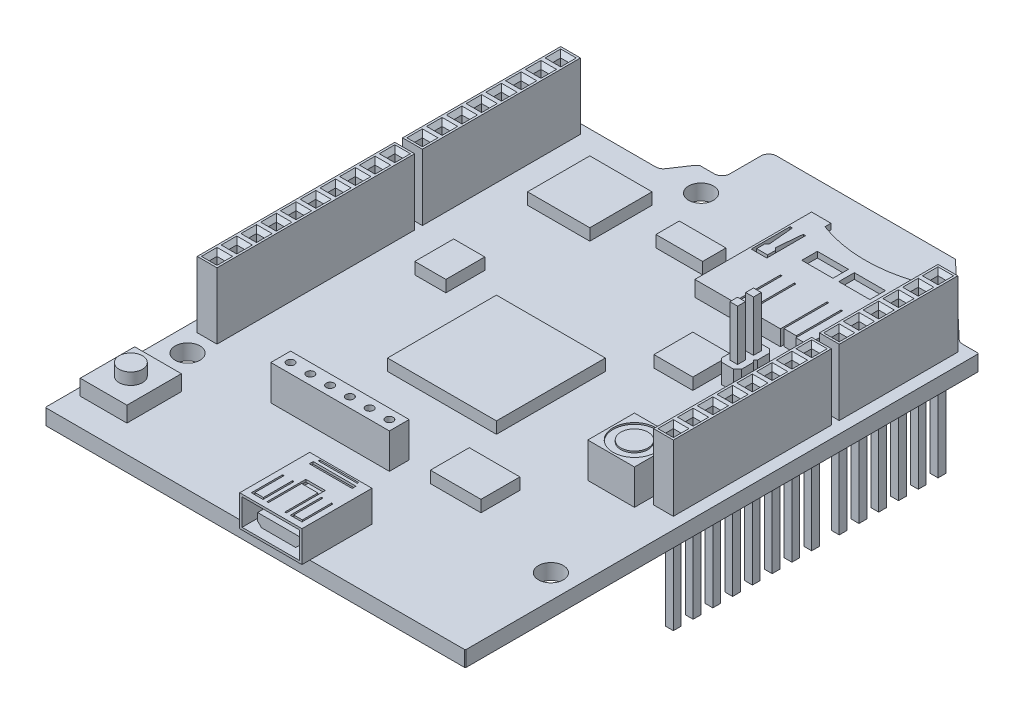
SolidWorks part; units mm, degrees
note: The reader was unsure of these and kept them because the rebuilt part matched: shared geometry of "Esquisse20<2>".
ref_plane "Plan de face" through (0, 0, 0) normal (0, 0, 1) x (1, 0, 0)
ref_plane "Plan de dessus" through (0, 0, 0) normal (0, 1, 0) x (1, 0, 0)
ref_plane "Plan de droite" through (0, 0, 0) normal (1, 0, 0) x (0, 0, -1)
ref_plane "Droite" through (54, 0, 0) normal (1, 0, 0) x (0, 0, -1)
ref_plane "Plaque" through (0, 0, -66) normal (0, 0, 1) x (1, 0, 0)
ref_plane "Arriere" through (0, 0, -75) normal (0, 0, 1) x (1, 0, 0)
ref_plane "Platine" through (0, 2, 0) normal (0, 1, 0) x (1, 0, 0)
ref_plane "Borne" through (0, -11.5, 0) normal (0, 1, 0) x (1, 0, 0)
sketch "Esquisse1" plane through (0, 0, 0) normal (0, 1, 0) x (1, 0, 0)
  line L0 (-55, 66) -> (55, 66) construction
  line L1 (0, 0) -> (54, 0)
  line L2 (0, 0) -> (0, 66)
  line L3 (0, 66) -> (13, 66)
  line L4 (54, 0) -> (54, 66)
  line L5 (54, -55) -> (54, 55) construction
  line L6 (51.5, 66) -> (42, 75)
  line L7 (-55, 75) -> (55, 75) construction
  line L8 (42, 75) -> (18, 75)
  line L9 (18, 75) -> (18, 69)
  line L10 (18, 69) -> (15, 69)
  line L11 (15, 69) -> (13, 66)
  line L12 (51.5, 66) -> (54, 66)
  dimension "D1" = 2.5
  dimension "D2" = 24
  dimension "D3" = 13
  dimension "D4" = 3
  dimension "D5" = 5
  dimension "D6" = 3
extrude "Boss.-Extru.1" add sketch "Esquisse1" along normal up to surface (2 mm away) up to plane "Platine"
sketch "Esquisse2" plane through (0, 2, 0) normal (0, 1, 0) x (1, 0, 0)
  line L0 (2.23, 60.49) -> (3.23, 60.49)
  line L1 (1.46, 64.8) -> (4, 64.8)
  line L2 (1.46, 64.8) -> (1.46, 44.48)
  line L3 (1.46, 44.48) -> (4, 44.48)
  line L4 (4, 64.8) -> (4, 44.48)
  line L5 (1.46, 43.48) -> (4, 43.48)
  line L6 (1.46, 43.48) -> (1.46, 18.08)
  line L7 (1.46, 18.08) -> (4, 18.08)
  line L8 (4, 43.48) -> (4, 18.08)
  line L9 (49.96, 64.8) -> (52.5, 64.8)
  line L10 (49.96, 64.8) -> (49.96, 49.56)
  line L11 (49.96, 49.56) -> (52.5, 49.56)
  line L12 (52.5, 64.8) -> (52.5, 49.56)
  line L13 (49.96, 48.56) -> (52.5, 48.56)
  line L14 (49.96, 48.56) -> (49.96, 28.24)
  line L15 (49.96, 28.24) -> (52.5, 28.24)
  line L16 (52.5, 48.56) -> (52.5, 28.24)
  line L17 (2.23, 63.03) -> (3.23, 63.03)
  line L18 (-1.1, 66) -> (1.1, 66) construction
  line L19 (54, -1.1) -> (54, 1.1) construction
  line L20 (2.73, 18.08) -> (2.73, 43.48) construction
  line L21 (2.73, 44.48) -> (2.73, 64.8) construction
  line L22 (51.23, 28.24) -> (51.23, 48.56) construction
  line L23 (51.23, 49.56) -> (51.23, 64.8) construction
  line L24 (2.23, 21.39) -> (3.23, 21.39)
  line L25 (2.23, 18.85) -> (3.23, 18.85)
  line L26 (2.23, 18.85) -> (2.23, 19.85)
  line L27 (2.23, 19.85) -> (3.23, 19.85)
  line L28 (3.23, 18.85) -> (3.23, 19.85)
  line L29 (2.23, 18.85) -> (3.23, 19.85) construction
  line L30 (2.23, 19.85) -> (3.23, 18.85) construction
  line L31 (2.23, 21.39) -> (2.23, 22.39)
  line L32 (2.23, 22.39) -> (3.23, 22.39)
  line L33 (3.23, 21.39) -> (3.23, 22.39)
  line L34 (2.23, 21.39) -> (3.23, 22.39) construction
  line L35 (2.23, 22.39) -> (3.23, 21.39) construction
  line L36 (2.23, 23.93) -> (3.23, 23.93)
  line L37 (2.23, 23.93) -> (2.23, 24.93)
  line L38 (2.23, 24.93) -> (3.23, 24.93)
  line L39 (3.23, 23.93) -> (3.23, 24.93)
  line L40 (2.23, 23.93) -> (3.23, 24.93) construction
  line L41 (2.23, 24.93) -> (3.23, 23.93) construction
  line L42 (2.23, 26.47) -> (3.23, 26.47)
  line L43 (2.23, 26.47) -> (2.23, 27.47)
  line L44 (2.23, 27.47) -> (3.23, 27.47)
  line L45 (3.23, 26.47) -> (3.23, 27.47)
  line L46 (2.23, 26.47) -> (3.23, 27.47) construction
  line L47 (2.23, 27.47) -> (3.23, 26.47) construction
  line L48 (2.23, 29.01) -> (3.23, 29.01)
  line L49 (2.23, 29.01) -> (2.23, 30.01)
  line L50 (2.23, 30.01) -> (3.23, 30.01)
  line L51 (3.23, 29.01) -> (3.23, 30.01)
  line L52 (2.23, 29.01) -> (3.23, 30.01) construction
  line L53 (2.23, 30.01) -> (3.23, 29.01) construction
  line L54 (2.23, 31.55) -> (3.23, 31.55)
  line L55 (2.23, 31.55) -> (2.23, 32.55)
  line L56 (2.23, 32.55) -> (3.23, 32.55)
  line L57 (3.23, 31.55) -> (3.23, 32.55)
  line L58 (2.23, 31.55) -> (3.23, 32.55) construction
  line L59 (2.23, 32.55) -> (3.23, 31.55) construction
  line L60 (2.23, 34.09) -> (3.23, 34.09)
  line L61 (2.23, 34.09) -> (2.23, 35.09)
  line L62 (2.23, 35.09) -> (3.23, 35.09)
  line L63 (3.23, 34.09) -> (3.23, 35.09)
  line L64 (2.23, 34.09) -> (3.23, 35.09) construction
  line L65 (2.23, 35.09) -> (3.23, 34.09) construction
  line L66 (2.23, 36.63) -> (3.23, 36.63)
  line L67 (2.23, 36.63) -> (2.23, 37.63)
  line L68 (2.23, 37.63) -> (3.23, 37.63)
  line L69 (3.23, 36.63) -> (3.23, 37.63)
  line L70 (2.23, 36.63) -> (3.23, 37.63) construction
  line L71 (2.23, 37.63) -> (3.23, 36.63) construction
  line L72 (2.23, 39.17) -> (3.23, 39.17)
  line L73 (2.23, 39.17) -> (2.23, 40.17)
  line L74 (2.23, 40.17) -> (3.23, 40.17)
  line L75 (3.23, 39.17) -> (3.23, 40.17)
  line L76 (2.23, 39.17) -> (3.23, 40.17) construction
  line L77 (2.23, 40.17) -> (3.23, 39.17) construction
  line L78 (2.23, 41.71) -> (3.23, 41.71)
  line L79 (2.23, 41.71) -> (2.23, 42.71)
  line L80 (2.23, 42.71) -> (3.23, 42.71)
  line L81 (3.23, 41.71) -> (3.23, 42.71)
  line L82 (2.23, 41.71) -> (3.23, 42.71) construction
  line L83 (2.23, 42.71) -> (3.23, 41.71) construction
  line L84 (2.23, 63.03) -> (2.23, 64.03)
  line L85 (2.23, 64.03) -> (3.23, 64.03)
  line L86 (3.23, 63.03) -> (3.23, 64.03)
  line L87 (2.23, 63.03) -> (3.23, 64.03) construction
  line L88 (2.23, 64.03) -> (3.23, 63.03) construction
  line L89 (2.23, 60.49) -> (2.23, 61.49)
  line L90 (2.23, 61.49) -> (3.23, 61.49)
  line L91 (3.23, 60.49) -> (3.23, 61.49)
  line L92 (2.23, 60.49) -> (3.23, 61.49) construction
  line L93 (2.23, 61.49) -> (3.23, 60.49) construction
  line L94 (2.23, 57.95) -> (3.23, 57.95)
  line L95 (2.23, 57.95) -> (2.23, 58.95)
  line L96 (2.23, 58.95) -> (3.23, 58.95)
  line L97 (3.23, 57.95) -> (3.23, 58.95)
  line L98 (2.23, 57.95) -> (3.23, 58.95) construction
  line L99 (2.23, 58.95) -> (3.23, 57.95) construction
  line L100 (2.23, 55.41) -> (3.23, 55.41)
  line L101 (2.23, 55.41) -> (2.23, 56.41)
  line L102 (2.23, 56.41) -> (3.23, 56.41)
  line L103 (3.23, 55.41) -> (3.23, 56.41)
  line L104 (2.23, 55.41) -> (3.23, 56.41) construction
  line L105 (2.23, 56.41) -> (3.23, 55.41) construction
  line L106 (2.23, 52.87) -> (3.23, 52.87)
  line L107 (2.23, 52.87) -> (2.23, 53.87)
  line L108 (2.23, 53.87) -> (3.23, 53.87)
  line L109 (3.23, 52.87) -> (3.23, 53.87)
  line L110 (2.23, 52.87) -> (3.23, 53.87) construction
  line L111 (2.23, 53.87) -> (3.23, 52.87) construction
  line L112 (2.23, 50.33) -> (3.23, 50.33)
  line L113 (2.23, 50.33) -> (2.23, 51.33)
  line L114 (2.23, 51.33) -> (3.23, 51.33)
  line L115 (3.23, 50.33) -> (3.23, 51.33)
  line L116 (2.23, 50.33) -> (3.23, 51.33) construction
  line L117 (2.23, 51.33) -> (3.23, 50.33) construction
  line L118 (2.23, 47.79) -> (3.23, 47.79)
  line L119 (2.23, 47.79) -> (2.23, 48.79)
  line L120 (2.23, 48.79) -> (3.23, 48.79)
  line L121 (3.23, 47.79) -> (3.23, 48.79)
  line L122 (2.23, 47.79) -> (3.23, 48.79) construction
  line L123 (2.23, 48.79) -> (3.23, 47.79) construction
  line L124 (2.23, 45.25) -> (3.23, 45.25)
  line L125 (2.23, 45.25) -> (2.23, 46.25)
  line L126 (2.23, 46.25) -> (3.23, 46.25)
  line L127 (3.23, 45.25) -> (3.23, 46.25)
  line L128 (2.23, 45.25) -> (3.23, 46.25) construction
  line L129 (2.23, 46.25) -> (3.23, 45.25) construction
  line L130 (50.73, 60.49) -> (51.73, 60.49)
  line L131 (50.73, 63.03) -> (51.73, 63.03)
  line L132 (50.73, 63.03) -> (50.73, 64.03)
  line L133 (50.73, 64.03) -> (51.73, 64.03)
  line L134 (51.73, 63.03) -> (51.73, 64.03)
  line L135 (50.73, 63.03) -> (51.73, 64.03) construction
  line L136 (50.73, 64.03) -> (51.73, 63.03) construction
  line L137 (50.73, 46.79) -> (51.73, 46.79)
  line L138 (50.73, 46.79) -> (50.73, 47.79)
  line L139 (50.73, 47.79) -> (51.73, 47.79)
  line L140 (51.73, 46.79) -> (51.73, 47.79)
  line L141 (50.73, 46.79) -> (51.73, 47.79) construction
  line L142 (50.73, 47.79) -> (51.73, 46.79) construction
  line L143 (50.73, 60.49) -> (50.73, 61.49)
  line L144 (50.73, 61.49) -> (51.73, 61.49)
  line L145 (51.73, 60.49) -> (51.73, 61.49)
  line L146 (50.73, 60.49) -> (51.73, 61.49) construction
  line L147 (50.73, 61.49) -> (51.73, 60.49) construction
  line L148 (50.73, 57.95) -> (51.73, 57.95)
  line L149 (50.73, 57.95) -> (50.73, 58.95)
  line L150 (50.73, 58.95) -> (51.73, 58.95)
  line L151 (51.73, 57.95) -> (51.73, 58.95)
  line L152 (50.73, 57.95) -> (51.73, 58.95) construction
  line L153 (50.73, 58.95) -> (51.73, 57.95) construction
  line L154 (50.73, 55.41) -> (51.73, 55.41)
  line L155 (50.73, 55.41) -> (50.73, 56.41)
  line L156 (50.73, 56.41) -> (51.73, 56.41)
  line L157 (51.73, 55.41) -> (51.73, 56.41)
  line L158 (50.73, 55.41) -> (51.73, 56.41) construction
  line L159 (50.73, 56.41) -> (51.73, 55.41) construction
  line L160 (50.73, 52.87) -> (51.73, 52.87)
  line L161 (50.73, 52.87) -> (50.73, 53.87)
  line L162 (50.73, 53.87) -> (51.73, 53.87)
  line L163 (51.73, 52.87) -> (51.73, 53.87)
  line L164 (50.73, 52.87) -> (51.73, 53.87) construction
  line L165 (50.73, 53.87) -> (51.73, 52.87) construction
  line L166 (50.73, 50.33) -> (51.73, 50.33)
  line L167 (50.73, 50.33) -> (50.73, 51.33)
  line L168 (50.73, 51.33) -> (51.73, 51.33)
  line L169 (51.73, 50.33) -> (51.73, 51.33)
  line L170 (50.73, 50.33) -> (51.73, 51.33) construction
  line L171 (50.73, 51.33) -> (51.73, 50.33) construction
  line L172 (50.73, 44.25) -> (51.73, 44.25)
  line L173 (50.73, 44.25) -> (50.73, 45.25)
  line L174 (50.73, 45.25) -> (51.73, 45.25)
  line L175 (51.73, 44.25) -> (51.73, 45.25)
  line L176 (50.73, 44.25) -> (51.73, 45.25) construction
  line L177 (50.73, 45.25) -> (51.73, 44.25) construction
  line L178 (50.73, 41.71) -> (51.73, 41.71)
  line L179 (50.73, 41.71) -> (50.73, 42.71)
  line L180 (50.73, 42.71) -> (51.73, 42.71)
  line L181 (51.73, 41.71) -> (51.73, 42.71)
  line L182 (50.73, 41.71) -> (51.73, 42.71) construction
  line L183 (50.73, 42.71) -> (51.73, 41.71) construction
  line L184 (50.73, 39.17) -> (51.73, 39.17)
  line L185 (50.73, 39.17) -> (50.73, 40.17)
  line L186 (50.73, 40.17) -> (51.73, 40.17)
  line L187 (51.73, 39.17) -> (51.73, 40.17)
  line L188 (50.73, 39.17) -> (51.73, 40.17) construction
  line L189 (50.73, 40.17) -> (51.73, 39.17) construction
  line L190 (50.73, 36.63) -> (51.73, 36.63)
  line L191 (50.73, 36.63) -> (50.73, 37.63)
  line L192 (50.73, 37.63) -> (51.73, 37.63)
  line L193 (51.73, 36.63) -> (51.73, 37.63)
  line L194 (50.73, 36.63) -> (51.73, 37.63) construction
  line L195 (50.73, 37.63) -> (51.73, 36.63) construction
  line L196 (50.73, 34.09) -> (51.73, 34.09)
  line L197 (50.73, 34.09) -> (50.73, 35.09)
  line L198 (50.73, 35.09) -> (51.73, 35.09)
  line L199 (51.73, 34.09) -> (51.73, 35.09)
  line L200 (50.73, 34.09) -> (51.73, 35.09) construction
  line L201 (50.73, 35.09) -> (51.73, 34.09) construction
  line L202 (50.73, 31.55) -> (51.73, 31.55)
  line L203 (50.73, 31.55) -> (50.73, 32.55)
  line L204 (50.73, 32.55) -> (51.73, 32.55)
  line L205 (51.73, 31.55) -> (51.73, 32.55)
  line L206 (50.73, 31.55) -> (51.73, 32.55) construction
  line L207 (50.73, 32.55) -> (51.73, 31.55) construction
  line L208 (50.73, 29.01) -> (51.73, 29.01)
  line L209 (50.73, 29.01) -> (50.73, 30.01)
  line L210 (50.73, 30.01) -> (51.73, 30.01)
  line L211 (51.73, 29.01) -> (51.73, 30.01)
  line L212 (50.73, 29.01) -> (51.73, 30.01) construction
  line L213 (50.73, 30.01) -> (51.73, 29.01) construction
  point P24 (2.73, 63.53)
  point P29 (2.73, 19.35)
  point P36 (2.73, 21.89)
  point P41 (2.73, 24.43)
  point P46 (2.73, 26.97)
  point P51 (2.73, 29.51)
  point P56 (2.73, 32.05)
  point P61 (2.73, 34.59)
  point P66 (2.73, 37.13)
  point P71 (2.73, 39.67)
  point P76 (2.73, 42.21)
  point P83 (51.23, 63.53)
  point P85 (2.73, 60.99)
  point P90 (2.73, 58.45)
  point P95 (2.73, 55.91)
  point P100 (2.73, 53.37)
  point P105 (2.73, 50.83)
  point P110 (2.73, 48.29)
  point P115 (2.73, 45.75)
  point P123 (51.23, 47.29)
  point P130 (51.23, 60.99)
  point P135 (51.23, 58.45)
  point P140 (51.23, 55.91)
  point P145 (51.23, 53.37)
  point P150 (51.23, 50.83)
  point P155 (51.23, 44.75)
  point P160 (51.23, 42.21)
  point P165 (51.23, 39.67)
  point P170 (51.23, 37.13)
  point P175 (51.23, 34.59)
  point P180 (51.23, 32.05)
  point P185 (51.23, 29.51)
  dimension "D2" = 1.5
  dimension "D3" = 1
  dimension "D4" = 6
  dimension "D5" = 1.27
  dimension "D6" = 1.27
  dimension "D7" = 48.5
  dimension "D8" = 1.2
  dimension "D9" = 2.54
  dimension "D10" = 1
  dimension "D11" = 1.27
  dimension "D12" = 25.4
  dimension "D13" = 1.27
  dimension "D14" = 1.27
  dimension "D15" = 1
  dimension "D16" = 1.27
  dimension "D18" = 20.32
  dimension "D19" = 8
  dimension "D20" = 2.54
  dimension "D21" = 2.54
  dimension "D22" = 2.54
  dimension "D24" = 2.54
  dimension "D25" = 1.27
  dimension "D17" = 10
  dimension "D23" = 8
extrude "Boss.-Extru.2" add sketch "Esquisse2" along normal blind 8.5
sketch "Esquisse3" plane through (0, 2, 0) normal (0, 1, 0) x (1, 0, 0)
  line L0 (18.3, 66) -> (46.2, 66) construction
  line L1 (-5.775, 66) -> (5.775, 66) construction
  line L2 (54, -5.775) -> (54, 5.775) construction
  line L3 (0, -5.775) -> (0, 5.775) construction
  circle A0 centre (18.3, 66) radius 1.6
  circle A1 centre (46.2, 66) radius 1.6
  circle A2 centre (50.9, 14.1) radius 1.6
  circle A3 centre (3.1, 15.2) radius 1.6
  dimension "D6" = 3.2
  dimension "D1" = 50.8
  dimension "D2" = 51.9
  dimension "D3" = 27.9
  dimension "D4" = 4.7
  dimension "D5" = 15.2
  dimension "D7" = 3.1
  dimension "D8" = 3.1
extrude "Enlèv. mat.-Extru.1" cut sketch "Esquisse3" against normal through all
sketch "Esquisse4" plane through (0, 0, 0) normal (0, 1, 0) x (1, 0, 0)
  line L0 (4, 64.8) -> (1.46, 64.8) construction
  line L1 (22.6, 67.14) -> (30.22, 67.14)
  line L2 (22.6, 67.14) -> (22.6, 62.06)
  line L3 (22.6, 62.06) -> (30.22, 62.06)
  line L4 (30.22, 67.14) -> (30.22, 62.06)
  line L5 (22.6, 67.14) -> (30.22, 62.06) construction
  line L6 (22.6, 62.06) -> (30.22, 67.14) construction
  line L7 (22.6, 64.6) -> (30.22, 64.6) construction
  line L8 (22.6, 65.87) -> (30.22, 65.87) construction
  line L9 (30.22, 63.33) -> (22.6, 63.33) construction
  line L10 (25.91, 62.83) -> (26.91, 62.83)
  line L11 (23.37, 62.83) -> (24.37, 62.83)
  line L12 (23.37, 62.83) -> (23.37, 63.83)
  line L13 (23.37, 63.83) -> (24.37, 63.83)
  line L14 (24.37, 62.83) -> (24.37, 63.83)
  line L15 (23.37, 62.83) -> (24.37, 63.83) construction
  line L16 (23.37, 63.83) -> (24.37, 62.83) construction
  line L17 (25.91, 62.83) -> (25.91, 63.83)
  line L18 (25.91, 63.83) -> (26.91, 63.83)
  line L19 (26.91, 62.83) -> (26.91, 63.83)
  line L20 (25.91, 62.83) -> (26.91, 63.83) construction
  line L21 (25.91, 63.83) -> (26.91, 62.83) construction
  line L22 (28.45, 62.83) -> (29.45, 62.83)
  line L23 (28.45, 62.83) -> (28.45, 63.83)
  line L24 (28.45, 63.83) -> (29.45, 63.83)
  line L25 (29.45, 62.83) -> (29.45, 63.83)
  line L26 (28.45, 62.83) -> (29.45, 63.83) construction
  line L27 (28.45, 63.83) -> (29.45, 62.83) construction
  line L28 (25.91, 65.37) -> (26.91, 65.37)
  line L29 (25.91, 65.37) -> (25.91, 66.37)
  line L30 (25.91, 66.37) -> (26.91, 66.37)
  line L31 (26.91, 65.37) -> (26.91, 66.37)
  line L32 (25.91, 65.37) -> (26.91, 66.37) construction
  line L33 (25.91, 66.37) -> (26.91, 65.37) construction
  line L34 (28.45, 65.37) -> (29.45, 65.37)
  line L35 (28.45, 65.37) -> (28.45, 66.37)
  line L36 (28.45, 66.37) -> (29.45, 66.37)
  line L37 (29.45, 65.37) -> (29.45, 66.37)
  line L38 (28.45, 65.37) -> (29.45, 66.37) construction
  line L39 (28.45, 66.37) -> (29.45, 65.37) construction
  line L40 (23.37, 65.37) -> (24.37, 65.37)
  line L41 (23.37, 65.37) -> (23.37, 66.37)
  line L42 (23.37, 66.37) -> (24.37, 66.37)
  line L43 (24.37, 65.37) -> (24.37, 66.37)
  line L44 (23.37, 65.37) -> (24.37, 66.37) construction
  line L45 (23.37, 66.37) -> (24.37, 65.37) construction
  line L46 (4, 44.48) -> (4, 64.8) construction
  point P0 (26.41, 64.6)
  point P13 (23.87, 63.33)
  point P20 (26.41, 63.33)
  point P25 (28.95, 63.33)
  point P30 (26.41, 65.87)
  point P35 (28.95, 65.87)
  point P40 (23.87, 65.87)
  dimension "D1" = 2.34
  dimension "D2" = 2.54
  dimension "D3" = 1.27
  dimension "D4" = 1.27
  dimension "D5" = 1
  dimension "D6" = 1.27
  dimension "D9" = 2.54
  dimension "D10" = 1.27
  dimension "D11" = 18.6
  dimension "D7" = 3
  dimension "D8" = 2
extrude "Boss.-Extru.3" add sketch "Esquisse4" against normal up to surface (11.5 mm away) up to plane "Borne"
sketch "Esquisse5" plane through (0, 2, 0) normal (0, 1, 0) x (1, 0, 0)
  line L0 (0, -12.1) -> (0, 12.1) construction
  line L1 (14, 15) -> (29.24, 15)
  line L2 (14, 15) -> (14, 17.54)
  line L3 (14, 17.54) -> (29.24, 17.54)
  line L4 (29.24, 15) -> (29.24, 17.54)
  line L5 (14, 15) -> (29.24, 17.54) construction
  line L6 (14, 17.54) -> (29.24, 15) construction
  line L7 (-12.1, 0) -> (12.1, 0) construction
  line L8 (14, 16.27) -> (29.24, 16.27) construction
  circle A0 centre (15.27, 16.27) radius 0.5
  circle A1 centre (17.81, 16.27) radius 0.5
  circle A2 centre (20.35, 16.27) radius 0.5
  circle A3 centre (22.89, 16.27) radius 0.5
  circle A4 centre (25.43, 16.27) radius 0.5
  circle A5 centre (27.97, 16.27) radius 0.5
  point P0 (21.62, 16.27)
  dimension "D6" = 1
  dimension "D1" = 2.54
  dimension "D2" = 14
  dimension "D3" = 15
  dimension "D4" = 15.24
  dimension "D5" = 1.27
  dimension "D9" = 1.27
  dimension "D7" = 6
extrude "Boss.-Extru.4" add sketch "Esquisse5" along normal blind 4.5
sketch "Esquisse6" plane through (0, 2, 0) normal (0, 1, 0) x (1, 0, 0)
  line L0 (27.97, 16.27) -> (33.24, 16.27) construction
  line L1 (18, 40) -> (32, 40)
  line L2 (18, 40) -> (18, 26)
  line L3 (18, 26) -> (32, 26)
  line L4 (32, 40) -> (32, 26)
  line L5 (8.5, 61.5) -> (16.5, 61.5)
  line L6 (8.5, 61.5) -> (8.5, 53.5)
  line L7 (8.5, 53.5) -> (16.5, 53.5)
  line L8 (16.5, 61.5) -> (16.5, 53.5)
  line L9 (21.5, 60) -> (27.5, 60)
  line L10 (21.5, 60) -> (21.5, 57)
  line L11 (21.5, 57) -> (27.5, 57)
  line L12 (27.5, 60) -> (27.5, 57)
  line L13 (9, 43.5) -> (13, 43.5)
  line L14 (9, 43.5) -> (9, 38.5)
  line L15 (9, 38.5) -> (13, 38.5)
  line L16 (13, 43.5) -> (13, 38.5)
  line L17 (34.74, 48.5) -> (39.74, 48.5)
  line L18 (34.74, 48.5) -> (34.74, 43.5)
  line L19 (34.74, 43.5) -> (39.74, 43.5)
  line L20 (39.74, 48.5) -> (39.74, 43.5)
  line L21 (33.24, 21.27) -> (39.74, 21.27)
  line L22 (33.24, 21.27) -> (33.24, 16.27)
  line L23 (33.24, 16.27) -> (39.74, 16.27)
  line L24 (39.74, 21.27) -> (39.74, 16.27)
  line L25 (29.24, 15) -> (29.24, 17.54) construction
  line L26 (-5.775, 0) -> (5.775, 0) construction
  line L27 (54, -12.375) -> (54, 12.375) construction
  dimension "D1" = 4
  dimension "D2" = 6.5
  dimension "D3" = 5
  dimension "D4" = 14
  dimension "D5" = 26
  dimension "D6" = 22
  dimension "D7" = 5
  dimension "D8" = 3.5
  dimension "D9" = 4
  dimension "D10" = 5
  dimension "D11" = 5
  dimension "D12" = 10
  dimension "D13" = 8
  dimension "D14" = 1.5
  dimension "D15" = 6
  dimension "D16" = 3
  dimension "D17" = 1.5
  dimension "D18" = 5
extrude "Boss.-Extru.5" add sketch "Esquisse6" along normal blind 1.5
sketch "Esquisse7" plane through (0, 2, 0) normal (0, 1, 0) x (1, 0, 0)
  line L0 (-12.1, 0) -> (12.1, 0) construction
  line L1 (1, 10.5) -> (7, 10.5)
  line L2 (1, 10.5) -> (1, 3.5)
  line L3 (1, 3.5) -> (7, 3.5)
  line L4 (7, 10.5) -> (7, 3.5)
  line L5 (0, -12.1) -> (0, 12.1) construction
  dimension "D1" = 7
  dimension "D2" = 6
  dimension "D3" = 3.5
  dimension "D4" = 1
extrude "Boss.-Extru.6" add sketch "Esquisse7" along normal blind 2
sketch "Esquisse8" plane through (0, 2, 0) normal (0, 1, 0) x (1, 0, 0)
  line L0 (7, 10.5) -> (1, 3.5) construction
  circle A0 centre (4, 7) radius 1.5
  dimension "D1" = 3
extrude "Boss.-Extru.7" add sketch "Esquisse8" along normal blind 3.5
sketch "Esquisse9" plane through (0, 2, 0) normal (0, 1, 0) x (1, 0, 0)
  line L0 (49.96, 28.24) -> (52.5, 28.24) construction
  line L1 (43, 32.74) -> (49, 32.74)
  line L2 (43, 32.74) -> (43, 26.74)
  line L3 (43, 26.74) -> (49, 26.74)
  line L4 (49, 32.74) -> (49, 26.74)
  line L5 (54, -12.375) -> (54, 12.375) construction
  dimension "D1" = 6
  dimension "D2" = 1.5
  dimension "D3" = 5
extrude "Boss.-Extru.8" add sketch "Esquisse9" along normal blind 4.5
sketch "Esquisse10" plane through (0, 6.5, 0) normal (0, 1, 0) x (1, 0, 0)
  line L0 (49, 32.74) -> (43, 26.74) construction
  circle A0 centre (46, 29.74) radius 1.75
  circle A1 centre (46, 29.74) radius 2.75
  dimension "D1" = 3.5
  dimension "D2" = 5.5
extrude "Enlèv. mat.-Extru.2" cut sketch "Esquisse10" against normal blind 0.2
sketch "Esquisse12" plane through (0, 0, 0) normal (0, 1, 0) x (1, 0, 0)
  line L0 (3.23, 63.03) -> (3.23, 64.03) construction
  line L1 (3.23, 64.03) -> (2.23, 64.03) construction
  line L2 (2.23, 64.03) -> (2.23, 63.03) construction
  line L3 (2.23, 63.03) -> (3.23, 63.03) construction
  line L4 (3.23, 60.49) -> (3.23, 61.49) construction
  line L5 (3.23, 61.49) -> (2.23, 61.49) construction
  line L6 (2.23, 61.49) -> (2.23, 60.49) construction
  line L7 (2.23, 60.49) -> (3.23, 60.49) construction
  line L8 (3.23, 57.95) -> (3.23, 58.95) construction
  line L9 (3.23, 58.95) -> (2.23, 58.95) construction
  line L10 (2.23, 58.95) -> (2.23, 57.95) construction
  line L11 (2.23, 57.95) -> (3.23, 57.95) construction
  line L12 (3.23, 55.41) -> (3.23, 56.41) construction
  line L13 (3.23, 56.41) -> (2.23, 56.41) construction
  line L14 (2.23, 56.41) -> (2.23, 55.41) construction
  line L15 (2.23, 55.41) -> (3.23, 55.41) construction
  line L16 (3.23, 52.87) -> (3.23, 53.87) construction
  line L17 (3.23, 53.87) -> (2.23, 53.87) construction
  line L18 (2.23, 53.87) -> (2.23, 52.87) construction
  line L19 (2.23, 52.87) -> (3.23, 52.87) construction
  line L20 (3.23, 50.33) -> (3.23, 51.33) construction
  line L21 (3.23, 51.33) -> (2.23, 51.33) construction
  line L22 (2.23, 51.33) -> (2.23, 50.33) construction
  line L23 (2.23, 50.33) -> (3.23, 50.33) construction
  line L24 (3.23, 47.79) -> (3.23, 48.79) construction
  line L25 (3.23, 48.79) -> (2.23, 48.79) construction
  line L26 (2.23, 48.79) -> (2.23, 47.79) construction
  line L27 (2.23, 47.79) -> (3.23, 47.79) construction
  line L28 (3.23, 45.25) -> (3.23, 46.25) construction
  line L29 (3.23, 46.25) -> (2.23, 46.25) construction
  line L30 (2.23, 46.25) -> (2.23, 45.25) construction
  line L31 (2.23, 45.25) -> (3.23, 45.25) construction
  line L32 (3.23, 41.71) -> (3.23, 42.71) construction
  line L33 (3.23, 42.71) -> (2.23, 42.71) construction
  line L34 (2.23, 42.71) -> (2.23, 41.71) construction
  line L35 (2.23, 41.71) -> (3.23, 41.71) construction
  line L36 (3.23, 39.17) -> (3.23, 40.17) construction
  line L37 (3.23, 40.17) -> (2.23, 40.17) construction
  line L38 (2.23, 40.17) -> (2.23, 39.17) construction
  line L39 (2.23, 39.17) -> (3.23, 39.17) construction
  line L40 (3.23, 36.63) -> (3.23, 37.63) construction
  line L41 (3.23, 37.63) -> (2.23, 37.63) construction
  line L42 (2.23, 37.63) -> (2.23, 36.63) construction
  line L43 (2.23, 36.63) -> (3.23, 36.63) construction
  line L44 (3.23, 34.09) -> (3.23, 35.09) construction
  line L45 (3.23, 35.09) -> (2.23, 35.09) construction
  line L46 (2.23, 35.09) -> (2.23, 34.09) construction
  line L47 (2.23, 34.09) -> (3.23, 34.09) construction
  line L48 (3.23, 31.55) -> (3.23, 32.55) construction
  line L49 (3.23, 32.55) -> (2.23, 32.55) construction
  line L50 (2.23, 32.55) -> (2.23, 31.55) construction
  line L51 (2.23, 31.55) -> (3.23, 31.55) construction
  line L52 (3.23, 29.01) -> (3.23, 30.01) construction
  line L53 (3.23, 30.01) -> (2.23, 30.01) construction
  line L54 (2.23, 30.01) -> (2.23, 29.01) construction
  line L55 (2.23, 29.01) -> (3.23, 29.01) construction
  line L56 (3.23, 26.47) -> (3.23, 27.47) construction
  line L57 (3.23, 27.47) -> (2.23, 27.47) construction
  line L58 (2.23, 27.47) -> (2.23, 26.47) construction
  line L59 (2.23, 26.47) -> (3.23, 26.47) construction
  line L60 (3.23, 23.93) -> (3.23, 24.93) construction
  line L61 (3.23, 24.93) -> (2.23, 24.93) construction
  line L62 (2.23, 24.93) -> (2.23, 23.93) construction
  line L63 (2.23, 23.93) -> (3.23, 23.93) construction
  line L64 (3.23, 21.39) -> (3.23, 22.39) construction
  line L65 (3.23, 22.39) -> (2.23, 22.39) construction
  line L66 (2.23, 22.39) -> (2.23, 21.39) construction
  line L67 (2.23, 21.39) -> (3.23, 21.39) construction
  line L68 (3.23, 18.85) -> (3.23, 19.85) construction
  line L69 (3.23, 19.85) -> (2.23, 19.85) construction
  line L70 (2.23, 19.85) -> (2.23, 18.85) construction
  line L71 (2.23, 18.85) -> (3.23, 18.85) construction
  line L72 (51.73, 29.01) -> (51.73, 30.01) construction
  line L73 (51.73, 30.01) -> (50.73, 30.01) construction
  line L74 (50.73, 30.01) -> (50.73, 29.01) construction
  line L75 (50.73, 29.01) -> (51.73, 29.01) construction
  line L76 (51.73, 31.55) -> (51.73, 32.55) construction
  line L77 (51.73, 32.55) -> (50.73, 32.55) construction
  line L78 (50.73, 32.55) -> (50.73, 31.55) construction
  line L79 (50.73, 31.55) -> (51.73, 31.55) construction
  line L80 (51.73, 34.09) -> (51.73, 35.09) construction
  line L81 (51.73, 35.09) -> (50.73, 35.09) construction
  line L82 (50.73, 35.09) -> (50.73, 34.09) construction
  line L83 (50.73, 34.09) -> (51.73, 34.09) construction
  line L84 (51.73, 36.63) -> (51.73, 37.63) construction
  line L85 (51.73, 37.63) -> (50.73, 37.63) construction
  line L86 (50.73, 37.63) -> (50.73, 36.63) construction
  line L87 (50.73, 36.63) -> (51.73, 36.63) construction
  line L88 (51.73, 39.17) -> (51.73, 40.17) construction
  line L89 (51.73, 40.17) -> (50.73, 40.17) construction
  line L90 (50.73, 40.17) -> (50.73, 39.17) construction
  line L91 (50.73, 39.17) -> (51.73, 39.17) construction
  line L92 (51.73, 41.71) -> (51.73, 42.71) construction
  line L93 (51.73, 42.71) -> (50.73, 42.71) construction
  line L94 (50.73, 42.71) -> (50.73, 41.71) construction
  line L95 (50.73, 41.71) -> (51.73, 41.71) construction
  line L96 (51.73, 44.25) -> (51.73, 45.25) construction
  line L97 (51.73, 45.25) -> (50.73, 45.25) construction
  line L98 (50.73, 45.25) -> (50.73, 44.25) construction
  line L99 (50.73, 44.25) -> (51.73, 44.25) construction
  line L100 (51.73, 46.79) -> (51.73, 47.79) construction
  line L101 (51.73, 47.79) -> (50.73, 47.79) construction
  line L102 (50.73, 47.79) -> (50.73, 46.79) construction
  line L103 (50.73, 46.79) -> (51.73, 46.79) construction
  line L104 (51.73, 50.33) -> (51.73, 51.33) construction
  line L105 (51.73, 51.33) -> (50.73, 51.33) construction
  line L106 (50.73, 51.33) -> (50.73, 50.33) construction
  line L107 (50.73, 50.33) -> (51.73, 50.33) construction
  line L108 (51.73, 52.87) -> (51.73, 53.87) construction
  line L109 (51.73, 53.87) -> (50.73, 53.87) construction
  line L110 (50.73, 53.87) -> (50.73, 52.87) construction
  line L111 (50.73, 52.87) -> (51.73, 52.87) construction
  line L112 (51.73, 55.41) -> (51.73, 56.41) construction
  line L113 (51.73, 56.41) -> (50.73, 56.41) construction
  line L114 (50.73, 56.41) -> (50.73, 55.41) construction
  line L115 (50.73, 55.41) -> (51.73, 55.41) construction
  line L116 (51.73, 57.95) -> (51.73, 58.95) construction
  line L117 (51.73, 58.95) -> (50.73, 58.95) construction
  line L118 (50.73, 58.95) -> (50.73, 57.95) construction
  line L119 (50.73, 57.95) -> (51.73, 57.95) construction
  line L120 (51.73, 60.49) -> (51.73, 61.49) construction
  line L121 (51.73, 61.49) -> (50.73, 61.49) construction
  line L122 (50.73, 61.49) -> (50.73, 60.49) construction
  line L123 (50.73, 60.49) -> (51.73, 60.49) construction
  line L124 (51.73, 63.03) -> (51.73, 64.03) construction
  line L125 (51.73, 64.03) -> (50.73, 64.03) construction
  line L126 (50.73, 64.03) -> (50.73, 63.03) construction
  line L127 (50.73, 63.03) -> (51.73, 63.03) construction
  line L128 (3.23, 63.03) -> (3.23, 64.03)
  line L129 (3.23, 64.03) -> (2.23, 64.03)
  line L130 (2.23, 64.03) -> (2.23, 63.03)
  line L131 (2.23, 63.03) -> (3.23, 63.03)
  line L132 (3.23, 60.49) -> (3.23, 61.49)
  line L133 (3.23, 61.49) -> (2.23, 61.49)
  line L134 (2.23, 61.49) -> (2.23, 60.49)
  line L135 (2.23, 60.49) -> (3.23, 60.49)
  line L136 (3.23, 57.95) -> (3.23, 58.95)
  line L137 (3.23, 58.95) -> (2.23, 58.95)
  line L138 (2.23, 58.95) -> (2.23, 57.95)
  line L139 (2.23, 57.95) -> (3.23, 57.95)
  line L140 (3.23, 55.41) -> (3.23, 56.41)
  line L141 (3.23, 56.41) -> (2.23, 56.41)
  line L142 (2.23, 56.41) -> (2.23, 55.41)
  line L143 (2.23, 55.41) -> (3.23, 55.41)
  line L144 (3.23, 52.87) -> (3.23, 53.87)
  line L145 (3.23, 53.87) -> (2.23, 53.87)
  line L146 (2.23, 53.87) -> (2.23, 52.87)
  line L147 (2.23, 52.87) -> (3.23, 52.87)
  line L148 (3.23, 50.33) -> (3.23, 51.33)
  line L149 (3.23, 51.33) -> (2.23, 51.33)
  line L150 (2.23, 51.33) -> (2.23, 50.33)
  line L151 (2.23, 50.33) -> (3.23, 50.33)
  line L152 (3.23, 47.79) -> (3.23, 48.79)
  line L153 (3.23, 48.79) -> (2.23, 48.79)
  line L154 (2.23, 48.79) -> (2.23, 47.79)
  line L155 (2.23, 47.79) -> (3.23, 47.79)
  line L156 (3.23, 45.25) -> (3.23, 46.25)
  line L157 (3.23, 46.25) -> (2.23, 46.25)
  line L158 (2.23, 46.25) -> (2.23, 45.25)
  line L159 (2.23, 45.25) -> (3.23, 45.25)
  line L160 (3.23, 41.71) -> (3.23, 42.71)
  line L161 (3.23, 42.71) -> (2.23, 42.71)
  line L162 (2.23, 42.71) -> (2.23, 41.71)
  line L163 (2.23, 41.71) -> (3.23, 41.71)
  line L164 (3.23, 39.17) -> (3.23, 40.17)
  line L165 (3.23, 40.17) -> (2.23, 40.17)
  line L166 (2.23, 40.17) -> (2.23, 39.17)
  line L167 (2.23, 39.17) -> (3.23, 39.17)
  line L168 (3.23, 36.63) -> (3.23, 37.63)
  line L169 (3.23, 37.63) -> (2.23, 37.63)
  line L170 (2.23, 37.63) -> (2.23, 36.63)
  line L171 (2.23, 36.63) -> (3.23, 36.63)
  line L172 (3.23, 34.09) -> (3.23, 35.09)
  line L173 (3.23, 35.09) -> (2.23, 35.09)
  line L174 (2.23, 35.09) -> (2.23, 34.09)
  line L175 (2.23, 34.09) -> (3.23, 34.09)
  line L176 (3.23, 31.55) -> (3.23, 32.55)
  line L177 (3.23, 32.55) -> (2.23, 32.55)
  line L178 (2.23, 32.55) -> (2.23, 31.55)
  line L179 (2.23, 31.55) -> (3.23, 31.55)
  line L180 (3.23, 29.01) -> (3.23, 30.01)
  line L181 (3.23, 30.01) -> (2.23, 30.01)
  line L182 (2.23, 30.01) -> (2.23, 29.01)
  line L183 (2.23, 29.01) -> (3.23, 29.01)
  line L184 (3.23, 26.47) -> (3.23, 27.47)
  line L185 (3.23, 27.47) -> (2.23, 27.47)
  line L186 (2.23, 27.47) -> (2.23, 26.47)
  line L187 (2.23, 26.47) -> (3.23, 26.47)
  line L188 (3.23, 23.93) -> (3.23, 24.93)
  line L189 (3.23, 24.93) -> (2.23, 24.93)
  line L190 (2.23, 24.93) -> (2.23, 23.93)
  line L191 (2.23, 23.93) -> (3.23, 23.93)
  line L192 (3.23, 21.39) -> (3.23, 22.39)
  line L193 (3.23, 22.39) -> (2.23, 22.39)
  line L194 (2.23, 22.39) -> (2.23, 21.39)
  line L195 (2.23, 21.39) -> (3.23, 21.39)
  line L196 (3.23, 18.85) -> (3.23, 19.85)
  line L197 (3.23, 19.85) -> (2.23, 19.85)
  line L198 (2.23, 19.85) -> (2.23, 18.85)
  line L199 (2.23, 18.85) -> (3.23, 18.85)
  line L200 (51.73, 29.01) -> (51.73, 30.01)
  line L201 (51.73, 30.01) -> (50.73, 30.01)
  line L202 (50.73, 30.01) -> (50.73, 29.01)
  line L203 (50.73, 29.01) -> (51.73, 29.01)
  line L204 (51.73, 31.55) -> (51.73, 32.55)
  line L205 (51.73, 32.55) -> (50.73, 32.55)
  line L206 (50.73, 32.55) -> (50.73, 31.55)
  line L207 (50.73, 31.55) -> (51.73, 31.55)
  line L208 (51.73, 34.09) -> (51.73, 35.09)
  line L209 (51.73, 35.09) -> (50.73, 35.09)
  line L210 (50.73, 35.09) -> (50.73, 34.09)
  line L211 (50.73, 34.09) -> (51.73, 34.09)
  line L212 (51.73, 36.63) -> (51.73, 37.63)
  line L213 (51.73, 37.63) -> (50.73, 37.63)
  line L214 (50.73, 37.63) -> (50.73, 36.63)
  line L215 (50.73, 36.63) -> (51.73, 36.63)
  line L216 (51.73, 39.17) -> (51.73, 40.17)
  line L217 (51.73, 40.17) -> (50.73, 40.17)
  line L218 (50.73, 40.17) -> (50.73, 39.17)
  line L219 (50.73, 39.17) -> (51.73, 39.17)
  line L220 (51.73, 41.71) -> (51.73, 42.71)
  line L221 (51.73, 42.71) -> (50.73, 42.71)
  line L222 (50.73, 42.71) -> (50.73, 41.71)
  line L223 (50.73, 41.71) -> (51.73, 41.71)
  line L224 (51.73, 44.25) -> (51.73, 45.25)
  line L225 (51.73, 45.25) -> (50.73, 45.25)
  line L226 (50.73, 45.25) -> (50.73, 44.25)
  line L227 (50.73, 44.25) -> (51.73, 44.25)
  line L228 (51.73, 46.79) -> (51.73, 47.79)
  line L229 (51.73, 47.79) -> (50.73, 47.79)
  line L230 (50.73, 47.79) -> (50.73, 46.79)
  line L231 (50.73, 46.79) -> (51.73, 46.79)
  line L232 (51.73, 50.33) -> (51.73, 51.33)
  line L233 (51.73, 51.33) -> (50.73, 51.33)
  line L234 (50.73, 51.33) -> (50.73, 50.33)
  line L235 (50.73, 50.33) -> (51.73, 50.33)
  line L236 (51.73, 52.87) -> (51.73, 53.87)
  line L237 (51.73, 53.87) -> (50.73, 53.87)
  line L238 (50.73, 53.87) -> (50.73, 52.87)
  line L239 (50.73, 52.87) -> (51.73, 52.87)
  line L240 (51.73, 55.41) -> (51.73, 56.41)
  line L241 (51.73, 56.41) -> (50.73, 56.41)
  line L242 (50.73, 56.41) -> (50.73, 55.41)
  line L243 (50.73, 55.41) -> (51.73, 55.41)
  line L244 (51.73, 57.95) -> (51.73, 58.95)
  line L245 (51.73, 58.95) -> (50.73, 58.95)
  line L246 (50.73, 58.95) -> (50.73, 57.95)
  line L247 (50.73, 57.95) -> (51.73, 57.95)
  line L248 (51.73, 60.49) -> (51.73, 61.49)
  line L249 (51.73, 61.49) -> (50.73, 61.49)
  line L250 (50.73, 61.49) -> (50.73, 60.49)
  line L251 (50.73, 60.49) -> (51.73, 60.49)
  line L252 (51.73, 63.03) -> (51.73, 64.03)
  line L253 (51.73, 64.03) -> (50.73, 64.03)
  line L254 (50.73, 64.03) -> (50.73, 63.03)
  line L255 (50.73, 63.03) -> (51.73, 63.03)
extrude "Boss.-Extru.9" add sketch "Esquisse12" against normal up to surface (11.5 mm away) up to plane "Borne"
sketch "Esquisse13" plane through (0, 2, 0) normal (0, 1, 0) x (1, 0, 0)
  line L0 (40.71, 48.29) -> (40.71, 46.25) construction
  line L1 (40.71, 50.33) -> (42.75, 50.33) construction
  line L2 (40.71, 50.33) -> (40.71, 48.29) construction
  line L3 (40.71, 48.29) -> (42.75, 48.29) construction
  line L4 (42.75, 50.33) -> (42.75, 48.29) construction
  line L5 (40.71, 46.25) -> (42.75, 46.25) construction
  line L6 (42.75, 46.25) -> (42.75, 48.29) construction
  line L7 (40.96, 50.58) -> (40.46, 50.08)
  line L8 (40.96, 50.58) -> (42.5, 50.58)
  line L9 (40.46, 50.08) -> (40.46, 48.54)
  line L10 (40.96, 46) -> (42.5, 46)
  line L11 (43, 50.08) -> (43, 48.54)
  line L12 (42.5, 50.58) -> (43, 50.08)
  line L13 (43, 46.5) -> (42.5, 46)
  line L14 (40.46, 46.5) -> (40.96, 46)
  line L15 (40.71, 48.29) -> (40.46, 48.54)
  line L16 (40.71, 48.29) -> (40.46, 48.04)
  line L17 (42.75, 48.29) -> (43, 48.54)
  line L18 (42.75, 48.29) -> (43, 48.04)
  line L19 (40.46, 48.04) -> (40.46, 46.5)
  line L20 (43, 48.04) -> (43, 46.5)
  line L21 (54, -12.375) -> (54, 12.375) construction
  line L22 (40.96, 46) -> (39.74, 46) construction
  line L23 (39.74, 43.5) -> (39.74, 48.5) construction
  dimension "D1" = 0.5
  dimension "D2" = 0.5
  dimension "D3" = 2.54
  dimension "D4" = 11
extrude "Boss.-Extru.10" add sketch "Esquisse13" along normal blind 2.5
sketch "Esquisse14" plane through (0, 2, 0) normal (0, 1, 0) x (1, 0, 0)
  line L0 (41.73, 49.81) -> (41.73, 50.58) construction
  line L1 (41.23, 49.81) -> (42.23, 49.81)
  line L2 (41.23, 49.81) -> (41.23, 48.81)
  line L3 (41.23, 48.81) -> (42.23, 48.81)
  line L4 (42.23, 49.81) -> (42.23, 48.81)
  line L5 (41.23, 47.77) -> (42.23, 47.77)
  line L6 (41.23, 47.77) -> (41.23, 46.77)
  line L7 (41.23, 46.77) -> (42.23, 46.77)
  line L8 (42.23, 47.77) -> (42.23, 46.77)
  line L9 (42.5, 50.58) -> (40.96, 50.58) construction
  line L10 (43, 47.27) -> (42.23, 47.27) construction
  line L11 (43, 46.5) -> (43, 48.04) construction
  line L12 (42.23, 49.31) -> (43, 49.31) construction
  line L13 (43, 48.54) -> (43, 50.08) construction
  dimension "D1" = 1
extrude "Boss.-Extru.11" add sketch "Esquisse14" along normal blind 9
sketch "Esquisse15" plane through (0, 2, 0) normal (0, 1, 0) x (1, 0, 0)
  line L0 (18, 69) -> (15, 69) construction
  line L1 (29.5, 69) -> (44, 69)
  line L2 (29.5, 69) -> (29.5, 54)
  line L3 (29.5, 54) -> (44, 54)
  line L4 (44, 69) -> (44, 54)
  line L5 (54, -12.375) -> (54, 12.375) construction
  dimension "D1" = 15
  dimension "D2" = 14.5
  dimension "D3" = 10
extrude "Boss.-Extru.12" add sketch "Esquisse15" along normal blind 2
sketch "Esquisse16" plane through (0, 2, 0) normal (0, 1, 0) x (1, 0, 0)
  line L0 (30.05, 66) -> (30.35, 62.7)
  line L1 (30.35, 62.7) -> (30.05, 62.4)
  line L2 (44, 54) -> (44, 69) construction
  line L3 (30.05, 62.4) -> (30.05, 61.4)
  line L4 (44, 69) -> (29.5, 69) construction
  line L5 (29.5, 69) -> (29.5, 54) construction
  line L6 (32, 68.225) -> (32, 69)
  line L7 (44, 69) -> (29.5, 69) construction
  line L8 (44, 69) -> (44, 68)
  line L9 (29.5, 54) -> (44, 54) construction
  line L10 (29.75, 66) -> (31.75, 66) construction
  line L11 (29.75, 66) -> (29.75, 61)
  line L12 (29.75, 61) -> (31.75, 61)
  line L13 (31.75, 66) -> (31.75, 61)
  line L14 (34.25, 65) -> (38.25, 65)
  line L15 (34.25, 65) -> (34.25, 63)
  line L16 (34.25, 63) -> (38.25, 63)
  line L17 (38.25, 65) -> (38.25, 63)
  line L18 (39, 65) -> (43, 65)
  line L19 (39, 65) -> (39, 63)
  line L20 (39, 63) -> (43, 63)
  line L21 (43, 65) -> (43, 63)
  line L22 (34.5, 60) -> (34.7, 60)
  line L23 (34.5, 60) -> (34.5, 54)
  line L24 (34.5, 54) -> (36.5, 54)
  line L25 (36.5, 60) -> (36.5, 54)
  line L26 (29.5, 69) -> (29.5, 54) construction
  line L27 (40.5, 60) -> (40.7, 60)
  line L28 (40.5, 60) -> (40.5, 54)
  line L29 (40.5, 54) -> (42.5, 54)
  line L30 (42.5, 60) -> (42.5, 54)
  line L31 (30.05, 61.4) -> (31.45, 61.4)
  line L32 (31.45, 61.4) -> (31.45, 62.4)
  line L33 (31.45, 62.4) -> (31.15, 62.7)
  line L34 (31.15, 62.7) -> (31.45, 66)
  line L35 (31.45, 66) -> (31.45, 62.4) construction
  line L36 (30.05, 66) -> (30.05, 62.4) construction
  line L37 (30.35, 62.7) -> (31.15, 62.7) construction
  line L38 (30.05, 62.4) -> (31.45, 62.4) construction
  line L39 (30.75, 66) -> (30.75, 61) construction
  line L40 (29.75, 66) -> (30.05, 66)
  line L41 (31.45, 66) -> (31.75, 66)
  line L42 (44, 54) -> (44, 69) construction
  line L43 (36.3, 60) -> (36.5, 60)
  line L44 (42.3, 60) -> (42.5, 60)
  line L45 (34.7, 60) -> (34.7, 54.25)
  line L46 (34.7, 54.25) -> (36.3, 54.25)
  line L47 (36.3, 60) -> (36.3, 54.25)
  line L48 (32, 69) -> (44, 69)
  line L49 (40.7, 60) -> (40.7, 54.25)
  line L50 (40.7, 54.25) -> (42.3, 54.25)
  line L51 (42.3, 60) -> (42.3, 54.25)
  arc A0 (44, 68) -> (32, 68.225) centre (38.3166, 85) cw
  point P48 (30.75, 62.4)
  point P49 (30.75, 62.7)
  dimension "D1" = 1
  dimension "D5" = 17.9249
  dimension "D2" = 2.5
  dimension "D3" = 16
  dimension "D4" = 0.775
  dimension "D6" = 2
  dimension "D7" = 4
  dimension "D8" = 1
  dimension "D9" = 0.75
  dimension "D10" = 4
  dimension "D11" = 2
  dimension "D12" = 0.25
  dimension "D13" = 3
  dimension "D14" = 5
  dimension "D15" = 0.3
  dimension "D16" = 0.3
  dimension "D17" = 0.4
  dimension "D18" = 1
  dimension "D19" = 0.2
  dimension "D20" = 0.25
  dimension "D21" = 1.5
  dimension "D22" = 2
  dimension "D23" = 6
  dimension "D24" = 6
extrude "Enlèv. mat.-Extru.3" cut sketch "Esquisse16" along normal through all
sketch "Esquisse17" plane through (0, 0, -66) normal (0, 0, 1) x (1, 0, 0)
  line L0 (29.7, 2) -> (-29.7, 2) construction
  line L1 (43.25, 3.25) -> (30.25, 3.25)
  line L2 (43.25, 3.25) -> (43.25, 2)
  line L3 (43.25, 2) -> (30.25, 2)
  line L4 (30.25, 3.25) -> (30.25, 2)
  line L5 (44, 4) -> (44, 2) construction
  line L6 (29.5, 4) -> (29.5, 2) construction
  dimension "D1" = 0.75
  dimension "D2" = 0.75
  dimension "D3" = 0.75
extrude "Enlèv. mat.-Extru.4" cut sketch "Esquisse17" against normal through all and the other way offset from surface (11.25 mm away) 0.75 other way up to face at (32, 3, -54)
sketch "Esquisse18" plane through (0, 2, 0) normal (0, 1, 0) x (1, 0, 0)
  line L0 (-12.375, 0) -> (12.375, 0) construction
  line L1 (26, 8) -> (34, 8)
  line L2 (26, 8) -> (26, -1)
  line L3 (26, -1) -> (34, -1)
  line L4 (34, 8) -> (34, -1)
  line L5 (54, -12.375) -> (54, 12.375) construction
  dimension "D1" = 8
  dimension "D2" = 9
  dimension "D3" = 1
  dimension "D4" = 20
extrude "Boss.-Extru.14" add sketch "Esquisse18" along normal blind 4
sketch "Esquisse19" plane through (0, 6, 0) normal (0, 1, 0) x (1, 0, 0)
  line L0 (26, -1) -> (34, -1) construction
  line L1 (27.5, 7.8) -> (32.5, 7.8)
  line L2 (27.5, 7.8) -> (27.5, 7.6)
  line L3 (27.5, 7.6) -> (32.5, 7.6)
  line L4 (32.5, 7.8) -> (32.5, 7.6)
  line L5 (27.25, 7.2) -> (32.75, 7.2)
  line L6 (27.25, 7.2) -> (27.25, 6.7)
  line L7 (27.25, 6.7) -> (32.75, 6.7)
  line L8 (32.75, 7.2) -> (32.75, 6.7)
  line L9 (31.75, 3.75) -> (31.95, 3.75)
  line L10 (31.75, 3.75) -> (31.75, -0.25)
  line L11 (31.75, -0.25) -> (33.25, -0.25)
  line L12 (33.25, 3.75) -> (33.25, -0.25)
  line L13 (34, 0) -> (34, 8) construction
  line L14 (31.95, 3.75) -> (31.95, 0)
  line L15 (31.95, 0) -> (33.05, 0)
  line L16 (33.05, 3.75) -> (33.05, 0)
  line L17 (26.75, 3.75) -> (26.95, 3.75)
  line L18 (26.75, 3.75) -> (26.75, -0.25)
  line L19 (26.75, -0.25) -> (28.25, -0.25)
  line L20 (28.25, 3.75) -> (28.25, -0.25)
  line L21 (31.05, -0.25) -> (31.25, -0.25)
  line L22 (26.95, 3.75) -> (26.95, 0)
  line L23 (26.95, 0) -> (28.05, 0)
  line L24 (28.05, 3.75) -> (28.05, 0)
  line L25 (28.75, -0.25) -> (28.95, -0.25)
  line L26 (28.75, -0.25) -> (28.75, 4.75)
  line L27 (28.75, 4.75) -> (31.25, 4.75)
  line L28 (31.25, -0.25) -> (31.25, 4.75)
  line L29 (33.05, 3.75) -> (33.25, 3.75)
  line L30 (28.95, -0.25) -> (28.95, 4)
  line L31 (28.95, 4) -> (31.05, 4)
  line L32 (31.05, -0.25) -> (31.05, 4)
  line L33 (-5.775, 0) -> (5.775, 0) construction
  line L34 (28.05, 3.75) -> (28.25, 3.75)
  line L35 (26, 8) -> (26, -1) construction
  line L36 (30, 4) -> (30, -1) construction
  line L37 (34, 8) -> (26, 8) construction
  line L38 (30, 7.2) -> (30, 7.6) construction
  line L39 (30, 7.8) -> (30, 8) construction
  line L40 (34, 8) -> (26, 8) construction
  dimension "D1" = 0.75
  dimension "D2" = 0.2
  dimension "D3" = 0.75
  dimension "D4" = 0.75
  dimension "D5" = 1.5
  dimension "D6" = 2.5
  dimension "D7" = 4
  dimension "D8" = 5
  dimension "D9" = 0.75
  dimension "D10" = 0.5
  dimension "D11" = 0.2
  dimension "D12" = 0.2
  dimension "D13" = 5.5
  dimension "D14" = 5
  dimension "D15" = 0.4
extrude "Enlèv. mat.-Extru.5" cut sketch "Esquisse19" against normal blind 0.5
sketch "Esquisse20" plane through (0, 0, 0) normal (0, 0, 1) x (1, 0, 0)
  line L0 (30, 6) -> (30, 2) construction
  line L1 (26.3, 5.7) -> (33.7, 5.7)
  line L2 (26.3, 5.7) -> (26.3, 2.3)
  line L3 (26.3, 2.3) -> (33.7, 2.3)
  line L4 (33.7, 5.7) -> (33.7, 2.3)
  line L5 (27.3, 3.95) -> (32.7, 3.95)
  line L6 (27.3, 3.95) -> (27.3, 2.5)
  line L7 (27.3, 2.5) -> (32.7, 2.5)
  line L8 (32.7, 3.95) -> (32.7, 2.5)
  line L11 (26, 6) -> (34, 6) construction
  line L12 (29.7, 2) -> (-29.7, 2) construction
  line L13 (34, 6) -> (34, 2) construction
  point P15 (30, 5.7)
  point P16 (30, 3.95)
  dimension "D1" = 0.3
  dimension "D2" = 0.3
  dimension "D3" = 0.3
  dimension "D4" = 0.2
  dimension "D5" = 1.75
  dimension "D6" = 1
extrude "Enlèv. mat.-Extru.6" cut sketch "Esquisse20" against normal offset from surface (7.7 mm away) 0.3 up to face at (30, 4, -8)
extrude "Enlèv. mat.-Extru.7" cut sketch "Esquisse20<2>" along normal through all contours L1 L4 L3 L2
sketch "Esquisse20<2>" plane through (0, 0, 0) normal (0, 0, 1) x (1, 0, 0) same geometry as "Esquisse20"
chamfer "Chanfrein1" distance 0.1 angle 45 5 edges at (15, 1, -69) (0, 1, -66) (0, 1, 0) (54, 1, 0) (54, 1, -66) first distance on face at (16.5, 1, -69) first distance on face at (0, 1, -33) first distance on face at (54, 1, -33)
chamfer "Chanfrein2" distance 0.5 angle 45 152 edges at (2.73, 10.5, -63.03) (2.23, 10.5, -63.53) (3.23, 10.5, -63.53) (2.73, 10.5, -64.03) (51.73, 10.5, -63.53) (51.23, 10.5, -64.03) (50.73, 10.5, -63.53) (51.23, 10.5, -63.03) (51.73, 10.5, -60.99) (51.23, 10.5, -61.49) (50.73, 10.5, -60.99) (51.23, 10.5, -60.49) (51.23, 10.5, -57.95) (50.73, 10.5, -58.45) (51.23, 10.5, -58.95) (51.73, 10.5, -58.45) (51.73, 10.5, -55.91) (51.23, 10.5, -55.41) (50.73, 10.5, -55.91) (51.23, 10.5, -56.41) (51.73, 10.5, -53.37) (51.23, 10.5, -53.87) (50.73, 10.5, -53.37) (51.23, 10.5, -52.87) (51.73, 10.5, -50.83) (51.23, 10.5, -50.33) (51.23, 10.5, -51.33) (50.73, 10.5, -50.83) (51.23, 10.5, -47.79) (50.73, 10.5, -47.29) (51.73, 10.5, -47.29) (51.23, 10.5, -46.79) (51.23, 10.5, -45.25) (51.73, 10.5, -44.75) (51.23, 10.5, -44.25) (50.73, 10.5, -44.75) (50.73, 10.5, -42.21) (51.23, 10.5, -42.71) (51.73, 10.5, -42.21) (51.23, 10.5, -41.71) (51.73, 10.5, -39.67) (51.23, 10.5, -39.17) (51.23, 10.5, -40.17) (50.73, 10.5, -39.67) (51.23, 10.5, -37.63) (50.73, 10.5, -37.13) (51.23, 10.5, -36.63) (51.73, 10.5, -37.13) (51.73, 10.5, -34.59) (51.23, 10.5, -35.09) (50.73, 10.5, -34.59) (51.23, 10.5, -34.09) (51.73, 10.5, -32.05) (51.23, 10.5, -32.55) (50.73, 10.5, -32.05) (51.23, 10.5, -31.55) (51.23, 10.5, -29.01) (51.73, 10.5, -29.51) (50.73, 10.5, -29.51) (51.23, 10.5, -30.01) (3.23, 10.5, -19.35) (2.73, 10.5, -18.85) (2.23, 10.5, -19.35) (2.73, 10.5, -19.85) (2.73, 10.5, -21.39) (3.23, 10.5, -21.89) (2.23, 10.5, -21.89) (2.73, 10.5, -22.39) (2.73, 10.5, -23.93) (3.23, 10.5, -24.43) (2.23, 10.5, -24.43) (2.73, 10.5, -24.93) (2.73, 10.5, -26.47) (3.23, 10.5, -26.97) (2.23, 10.5, -26.97) (2.73, 10.5, -27.47) (2.73, 10.5, -29.01) (3.23, 10.5, -29.51) (2.23, 10.5, -29.51) (2.73, 10.5, -30.01) (2.73, 10.5, -31.55) (3.23, 10.5, -32.05) (2.23, 10.5, -32.05) (2.73, 10.5, -32.55) (2.73, 10.5, -34.09) (3.23, 10.5, -34.59) (2.23, 10.5, -34.59) (2.73, 10.5, -35.09) (3.23, 10.5, -37.13) (2.73, 10.5, -36.63) (2.23, 10.5, -37.13) (2.73, 10.5, -37.63) (2.73, 10.5, -39.17) (3.23, 10.5, -39.67) (2.23, 10.5, -39.67) (2.73, 10.5, -40.17) (2.73, 10.5, -41.71) (3.23, 10.5, -42.21) (2.23, 10.5, -42.21) (2.73, 10.5, -42.71) (3.23, 10.5, -45.75) (2.73, 10.5, -45.25) (2.23, 10.5, -45.75) (2.73, 10.5, -46.25) (2.73, 10.5, -47.79) (3.23, 10.5, -48.29) (2.23, 10.5, -48.29) (2.73, 10.5, -48.79) (2.73, 10.5, -50.33) (3.23, 10.5, -50.83) (2.23, 10.5, -50.83) (2.73, 10.5, -51.33) (2.73, 10.5, -52.87) (3.23, 10.5, -53.37) (2.23, 10.5, -53.37) (2.73, 10.5, -53.87) (2.73, 10.5, -55.41) (3.23, 10.5, -55.91) (2.23, 10.5, -55.91) (2.73, 10.5, -56.41) (2.73, 10.5, -57.95) (3.23, 10.5, -58.45) (2.23, 10.5, -58.45) (2.73, 10.5, -58.95) (3.23, 10.5, -60.99) (2.73, 10.5, -60.49) (2.23, 10.5, -60.99) (2.73, 10.5, -61.49) (24.37, -11.5, -63.33) (23.87, -11.5, -62.83) (23.37, -11.5, -63.33) (23.87, -11.5, -63.83) (26.91, -11.5, -63.33) (26.41, -11.5, -62.83) (25.91, -11.5, -63.33) (26.41, -11.5, -63.83) (29.45, -11.5, -63.33) (28.95, -11.5, -62.83) (28.45, -11.5, -63.33) (28.95, -11.5, -63.83) (29.45, -11.5, -65.87) (28.95, -11.5, -65.37) (28.45, -11.5, -65.87) (28.95, -11.5, -66.37) (26.91, -11.5, -65.87) (26.41, -11.5, -65.37) (25.91, -11.5, -65.87) (26.41, -11.5, -66.37) (24.37, -11.5, -65.87) (23.87, -11.5, -65.37) (23.37, -11.5, -65.87) (23.87, -11.5, -66.37)
chamfer "Chanfrein3" distance 0.5 angle 45 2 edges at (32.7, 2.5, -3.85) (27.3, 2.5, -3.85)
fillet "Congé1" radius 1 4 edges at (51.5, 1, -66) (13, 1, -66) (18, 1, -75) (18, 1, -69)
